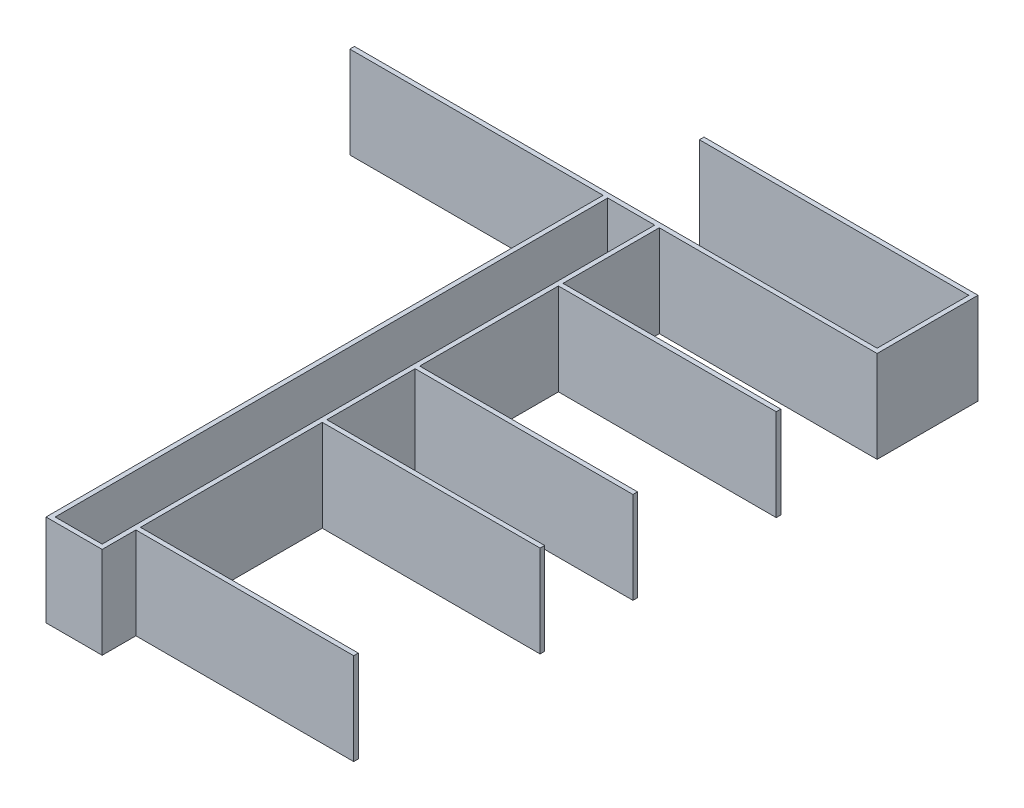
SolidWorks part; units mm, degrees
ref_plane "Front Plane" through (0, 0, 0) normal (0, 0, 1) x (1, 0, 0)
ref_plane "Top Plane" through (0, 0, 0) normal (0, 1, 0) x (1, 0, 0)
ref_plane "Right Plane" through (0, 0, 0) normal (1, 0, 0) x (0, 0, -1)
sketch "Sketch1" plane through (0, 0, 0) normal (0, 1, 0) x (1, 0, 0)
  line L0 (0, 14.7) -> (95, 14.7)
  line L1 (0, 0) -> (95, 0)
  line L2 (0, 0) -> (0, 245)
  line L3 (0, 245) -> (95, 245)
  line L4 (95, 0) -> (95, 245)
  line L5 (0, 16.7) -> (95, 16.7)
  line L6 (0, 243) -> (95, 243)
  line L7 (95, 0) -> (0, 0)
  line L11 (0, 96) -> (95, 96)
  line L12 (0, 96) -> (0, 98)
  line L13 (0, 98) -> (95, 98)
  line L14 (95, 96) -> (95, 98)
  line L15 (0, 136.5) -> (95, 136.5)
  line L16 (0, 136.5) -> (0, 138.5)
  line L17 (0, 138.5) -> (95, 138.5)
  line L18 (95, 136.5) -> (95, 138.5)
  line L19 (0, 199) -> (95, 199)
  line L20 (0, 199) -> (0, 201)
  line L21 (0, 201) -> (95, 201)
  line L22 (95, 199) -> (95, 201)
  line L23 (93, 285) -> (93, 245)
  line L24 (0, 245) -> (-2, 245)
  line L25 (0, 245) -> (0, 0)
  line L26 (0, 0) -> (-2, 0)
  line L27 (-2, 245) -> (-2, 0)
  line L28 (-2, 0) -> (-22.5, 0)
  line L29 (-2, 0) -> (-2, 245)
  line L30 (-2, 245) -> (-22.5, 245)
  line L31 (-22.5, 0) -> (-22.5, 245)
  line L32 (-22.5, 245) -> (-24.5, 245)
  line L33 (-22.5, 245) -> (-22.5, 0)
  line L34 (-22.5, 0) -> (-24.5, 0)
  line L35 (-24.5, 245) -> (-24.5, 0)
  line L36 (0, 243) -> (-24.5, 243)
  line L37 (0, 243) -> (0, 245)
  line L38 (0, 245) -> (-24.5, 245)
  line L39 (-24.5, 243) -> (-24.5, 245)
  line L40 (95, 245) -> (-24.5, 245)
  line L41 (95, 245) -> (95, 285)
  line L42 (95, 285) -> (-24.5, 285)
  line L43 (-24.5, 245) -> (-24.5, 285)
  line L45 (-24.5, 285) -> (95, 285)
  line L46 (-24.5, 285) -> (-24.5, 287)
  line L47 (-24.5, 287) -> (95, 287)
  line L48 (95, 285) -> (95, 287)
  line L50 (-24.5, 287) -> (-24.5, 285)
  line L53 (-24.5, 245) -> (-135, 245)
  line L54 (-24.5, 245) -> (-24.5, 243)
  line L55 (-24.5, 243) -> (-135, 243)
  line L56 (-135, 245) -> (-135, 243)
  line L57 (-22.5, 0) -> (-2, 0)
  line L58 (-22.5, 0) -> (-22.5, 2)
  line L59 (-22.5, 2) -> (-2, 2)
  line L60 (-2, 0) -> (-2, 2)
  dimension "D1" = 95
  dimension "D2" = 245
  dimension "D3" = 14.7
  dimension "D4" = 2
  dimension "D5" = 2
  dimension "D6" = 2
  dimension "D7" = 2
  dimension "D8" = 2
  dimension "D9" = 79.3
  dimension "D10" = 38.5
  dimension "D11" = 60.5
  dimension "D12" = 2
  dimension "D13" = 20.5
  dimension "D14" = 2
  dimension "D15" = 40
  dimension "D16" = 2
  dimension "D17" = 2
  dimension "D18" = 110.5
  dimension "D19" = 2
extrude "Boss-Extrude1" add sketch "Sketch1" along normal blind 40 contours L53 L56 L55 L35 | L42 L48 L47 L46 | L41 L42 L23 L3 | L2 L6 L4 L3 | L36 L27 L30 L33 | L36 L2 L24 L27 | L2 L36 L29 L26 | L36 L33 L32 L35 | L31 L36 L35 L34 | L17 L2 L15 L4 | L13 L2 L11 L4 | L5 L2 L0 L4 | L21 L22 L19 L20 region at (47.5, 0, -15.7) region at (-1, 0, -121.5) region at (47.5, 0, -97) region at (-23.5, 0, -121.5) region at (-12.25, 0, -244) region at (-1, 0, -244) region at (47.5, 0, -137.5) region at (47.5, 0, -244) region at (-23.5, 0, -244) region at (-79.75, 0, -244) region at (94, 0, -265) region at (35.25, 0, -286)
extrude "Boss-Extrude2" add sketch "Sketch1<4>" along normal blind 40 contours L59 L31 L28 L27 region at (-12.25, 0, -1)
sketch "Sketch1<4>" plane through (0, 0, 0) normal (0, 1, 0) x (1, 0, 0) same geometry as "Sketch1"
